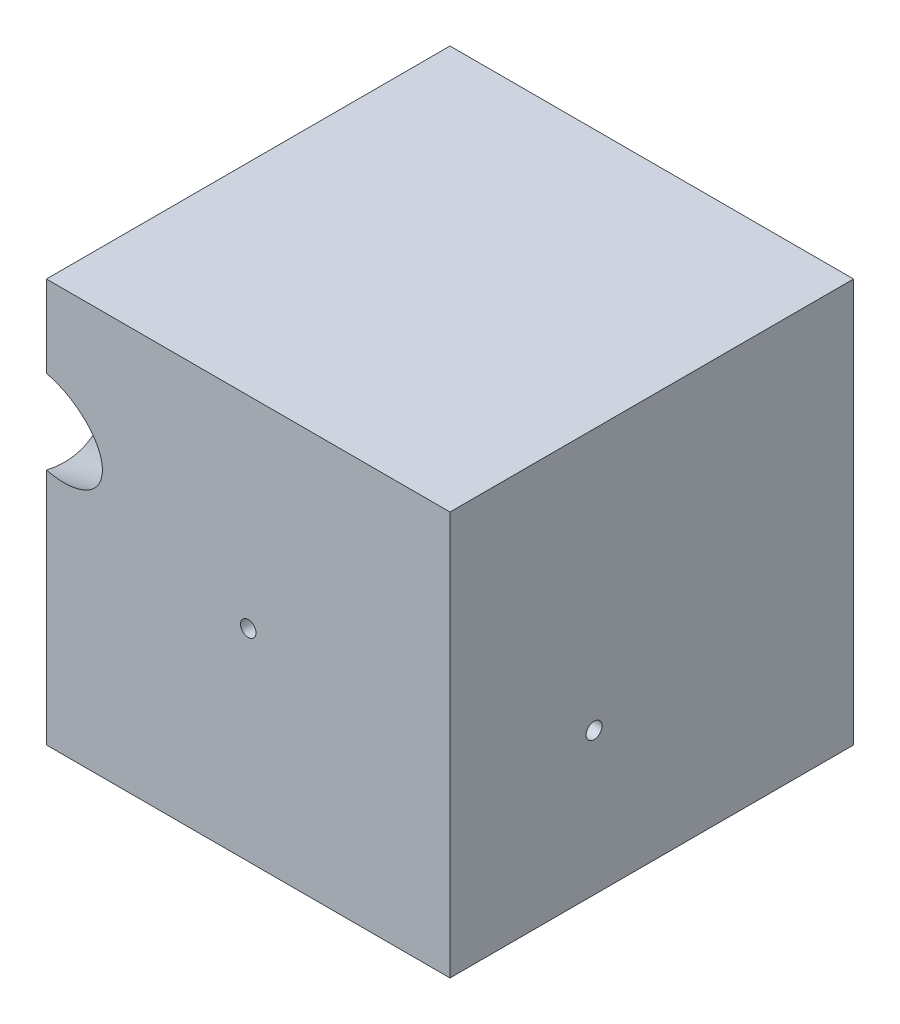
SolidWorks part; units mm, degrees
other "Markup1"
sketch "Sketch17" plane through (26, 26, 0) normal (0.2144, 0.2359, -0.9478) x (-0.9746, -0.0125, -0.2235)
other "Markup2"
sketch "Sketch18" plane through (26, 26, 52) normal (0.7408, 0.3225, 0.5893) x (0.4554, 0.4038, -0.7934)
other "Markup3"
sketch "Sketch19" plane through (-26, 26, 52) normal (-0.3816, 0.4867, 0.7858) x (0.9196, 0.2861, 0.2694)
material "ABS"
ref_plane "Front Plane" through (0, 0, 0) normal (0, 0, 1) x (1, 0, 0)
ref_plane "Top Plane" through (0, 0, 0) normal (0, 1, 0) x (1, 0, 0)
ref_plane "Right Plane" through (0, 0, 0) normal (1, 0, 0) x (0, 0, -1)
sketch "Square" plane through (0, 0, 0) normal (0, 0, 1) x (1, 0, 0)
  line L1 (-26, -26) -> (26, -26)
  line L2 (-26, -26) -> (-26, 26)
  line L3 (-26, 26) -> (26, 26)
  line L4 (26, -26) -> (26, 26)
  line L5 (-26, -26) -> (26, 26) construction
  line L6 (-26, 26) -> (26, -26) construction
  point P0 (0, 0)
  dimension "D1" = 52
extrude "Cube-Extrusion" add sketch "Square" along normal blind 52
ref_plane "StickPlane" through (-28.8889, 14.4444, 28.8889) normal (0.6667, -0.3333, -0.6667) x (-0.7454, -0.2981, -0.5963)
sketch "Stick-Hole" plane through (-28.8889, 14.4444, 28.8889) normal (0.6667, -0.3333, -0.6667) x (-0.7454, -0.2981, -0.5963)
  line L0 (-19.3793, 0) -> (-3.8759, -46.5102) construction
  circle A0 centre (-14.6358, -14.2302) radius 5.1
  dimension "D2" = 10.2
  dimension "D1" = 15
extrude "Stick-Cut" cut sketch "Stick-Hole" against normal through all from offset 15
sketch "Sketch12" plane through (0, 0, 52) normal (0, 0, 1) x (1, 0, 0)
  circle A0 centre (0, 0) radius 1
  dimension "D1" = 2
extrude "Cut-Extrude8" cut sketch "Sketch12" against normal blind 12
sketch "Sketch13" plane through (0, 0, 0) normal (0, 0, -1) x (-1, 0, 0)
  circle A0 centre (0, 0) radius 1
  dimension "D1" = 2
extrude "Cut-Extrude9" cut sketch "Sketch13" against normal blind 12
sketch "Sketch14" plane through (-26, 0, 0) normal (-1, 0, 0) x (0, 0, 1)
  line L0 (0, 26) -> (0, -26) construction
  line L1 (52, 26) -> (0, 26) construction
  line L2 (52, -26) -> (0, -26) construction
  circle A0 centre (10.5144, 15.4825) radius 1
  circle A1 centre (20.4493, -13.8146) radius 1
  dimension "D1" = 2
  dimension "D2" = 10.5144
  dimension "D3" = 10.5175
  dimension "D4" = 20.4493
  dimension "D5" = 12.1854
extrude "Cut-Extrude10" cut sketch "Sketch14" against normal blind 12
sketch "Sketch15" plane through (26, 0, 0) normal (1, 0, 0) x (0, 0, -1)
  circle A0 centre (-33.4399, -7.6506) radius 1.0307
extrude "Cut-Extrude11" cut sketch "Sketch15" against normal blind 12
sketch "Sketch16" plane through (0, -26, 0) normal (0, -1, 0) x (1, 0, 0)
  line L0 (-26, 52) -> (-26, 0) construction
  line L1 (-26, 0) -> (26, 0) construction
  circle A0 centre (-9, 44.28) radius 1
  dimension "D3" = 2
  dimension "D1" = 17
  dimension "D2" = 44.28
extrude "Cut-Extrude12" cut sketch "Sketch16" against normal blind 12
ref_plane "Plane1" through (0, 0, 0) normal (0.2823, 0.9593, 0) x (0.9593, -0.2823, 0)
